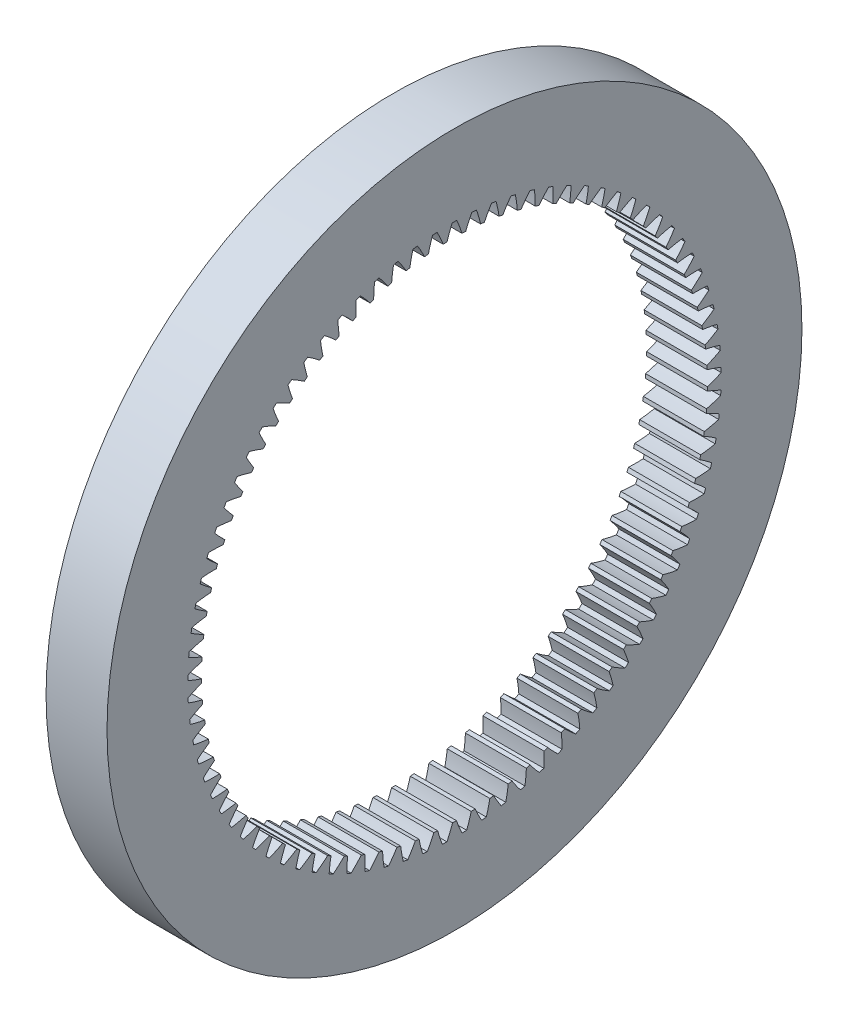
SolidWorks part; units mm, degrees
ref_plane "Plane1" through (0, 0, 0) normal (0, 0, 1) x (1, 0, 0)
ref_plane "Plane2" through (0, 0, 0) normal (0, 1, 0) x (1, 0, 0)
ref_plane "Plane3" through (0, 0, 0) normal (1, 0, 0) x (0, 0, -1)
sketch "HoldingSke" plane through (0, 0, 0) normal (0, 1, 0) x (1, 0, 0)
  line L0 (0, 0) -> (0.1743, -1.9924)
  line L1 (-15, 0) -> (100, 0) construction
  line L2 (0, 0) -> (-2.1039, 2.3779)
  line L3 (0, 0) -> (-11.863, 4.5341)
  line L4 (0, 0) -> (0.7527, 8.6031)
  line L5 (0, 0) -> (-23.7986, -8.8762)
  line L6 (0, 0) -> (-10.5278, -7.1032)
  line L7 (-2.1039, 2.3779) -> (3.3635, 27.1825)
  line L8 (-76.2, 2.8779) -> (-54.61, 2.8779)
  line L9 (-71.009, 38.7566) -> (-53.1078, 45.2721)
  line L10 (-76.2, 71.12) -> (104.1128, 71.12)
  line L11 (0, 0) -> (-5, 0)
  line L12 (-76.2, 101.6) -> (-76.181, 101.6)
  line L13 (24.9733, 27.94) -> (52.9518, 28.4284)
  line L14 (24.9733, 27.94) -> (24.9743, 27.94)
  line L15 (24.9733, 27.94) -> (100.4006, 29.5858)
  circle A0 centre (0, 0) radius 28.5
  circle A1 centre (0, 0) radius 12.7
  circle A2 centre (0, 0) radius 12.7
  dimension "Num_teeth" = 85
  dimension "Pitch_radius" = 180.3128
  dimension "Width" = 5
  dimension "Diameter" = 57
sketch "BasProSke" plane through (0, 0, 0) normal (0, 1, 0) x (1, 0, 0)
  line L0 (-10, 0) -> (60, 0) construction
  line L1 (0, 20.75) -> (0, 28.5)
  line L2 (0, 20.75) -> (5, 20.75)
  line L3 (5, 20.75) -> (5, 28.5)
  line L4 (5, 28.5) -> (0, 28.5)
  dimension "Thickness" = 5
  dimension "Diameter" = 57
revolve "Base-Revolve" add sketch "BasProSke" angle 360 about L0
sketch "TooCutSke" plane through (0, 0, 0) normal (1, 0, 0) x (0, 0, -1)
  line L3 (0.4402, 21.2454) -> (0.4402, 53.6633) construction
  line L4 (0, 0) -> (0, 59.563) construction
  line L5 (0, 0) -> (-2.5248, 68.2808) construction
  line L6 (-9.551, 17.6307) -> (37.1529, 19.3577) construction
  circle A0 centre (0, 0) radius 21.25 construction
  circle A1 centre (0, 0) radius 21.876 construction
  circle A2 centre (0, 0) radius 17.9716 construction
  circle A3 centre (0, 0) radius 20.7246 construction
  arc A4 (0.6163, 20.7154) -> (0.1893, 21.8752) centre (-9.551, 17.6307) ccw
  arc A5 (0.6163, 20.7154) -> (-0.6163, 20.7154) centre (0, 0) ccw
  arc A6 (0.1893, 21.8752) -> (-0.1893, 21.8752) centre (0, 0) ccw
  arc A7 (-0.1893, 21.8752) -> (-0.6163, 20.7154) centre (9.551, 17.6307) ccw
extrude "ToothCut" cut sketch "TooCutSke" along normal through all
fillet "Breaks" [suppressed] radius 0.05
fillet "RootFillets" [suppressed] radius 0.126
pattern_circular "TeethCuts" count 85 every 4.235 about axis through (-10, 0, 0) along (1, 0, 0) of "RootFillets", "Breaks", "ToothCut"
equation "' \"Module@HoldingSke\" = 6.35"
equation "' \"Num_teeth@HoldingSke\" = 24"
equation "' \"Ap@HoldingSke\" =  14.5"
equation "' \"Ap@HoldingSke\" = 14.5"
equation "' \"Width@HoldingSke\" = 12"
equation "' \"Diameter@HoldingSke\" = 8 * 25.4"
equation "' \"Show_teeth@HoldingSke\" = 100"
equation "' \"Backlash@HoldingSke\" = 0.009 * 25.4"
equation "' \"Addendum_fac@HoldingSke\" = 1.0"
equation "' \"Dedendum_fac@HoldingSke\" = 1.25"
equation "' \"Dedendum_add@HoldingSke\" = 0.00005 * 25.4"
equation "' \"Clearance_fac@HoldingSke\" = 0.25"
equation "\"Pitch@HoldingSke\" = 1 / \"Module@HoldingSke\" "
equation "\"Overcut_dia@TooCutSke\" = (\"Num_teeth@HoldingSke\" - 2 * \"Addendum_fac@HoldingSke\") / \"Pitch@HoldingSke\" - 0.002 * 25.4"
equation "\"Pitch_dia@TooCutSke\" = \"Num_teeth@HoldingSke\" / \"Pitch@HoldingSke\""
equation "\"Base_dia@TooCutSke\" = \"Num_teeth@HoldingSke\" / \"Pitch@HoldingSke\" * cos((\"Ap@HoldingSke\"  * 3.14159265 / 180)) * 0.90"
equation "\"Root_dia@TooCutSke\" = \"Num_teeth@HoldingSke\"  / \"Pitch@HoldingSke\" + 2 *  \"Dedendum_fac@HoldingSke\"/ \"Pitch@HoldingSke\" + \"Dedendum_add@HoldingSke\" * 2"
equation "\"Half_ang@TooCutSke\" = 180 / \"Num_teeth@HoldingSke\""
equation "\"Half_CT@TooCutSke\" = \"Num_teeth@HoldingSke\" / \"Pitch@HoldingSke\" * sin((3.14159265 / 2 / \"Num_teeth@HoldingSke\")) / 2 + 10 * \"Backlash@HoldingSke\" / 4"
equation "\"Flank_rad@TooCutSke\" = \"Num_teeth@HoldingSke\" / \"Pitch@HoldingSke\" / 4"
equation "\"Radius@RootFillets\"= \"Clearance_fac@HoldingSke\" / \"Pitch@HoldingSke\" + \"Dedendum_add@HoldingSke\""
equation "\"Break_rad@Breaks\" = 0.02 / \"Pitch@HoldingSke\" * 5"
equation "\"Num_teeth@TeethCuts\" = int( \"Show_teeth@HoldingSke\" ) + 1"
equation "\"Num_teeth@TeethCuts\" = ((sgn( \"Num_teeth@TeethCuts\" - \"Num_teeth@HoldingSke\" )-1)*( \"Num_teeth@TeethCuts\" - \"Num_teeth@HoldingSke\" ))/-2+ \"Num_teeth@HoldingSke\""
equation "\"Num_teeth@TeethCuts\" = ((sgn( \"Num_teeth@TeethCuts\" - 2.0)+1)*( \"Num_teeth@TeethCuts\" - 2.0))/2 +2.0"
equation "\"Angle@TeethCuts\" = 360.0 / \"Num_teeth@HoldingSke\""
equation "\"Diameter@BasProSke\" = \"Num_teeth@HoldingSke\"  / \"Pitch@HoldingSke\" + 2 *  \"Dedendum_fac@HoldingSke\"/ \"Pitch@HoldingSke\" + \"Dedendum_add@HoldingSke\" * 2 + 0.002 * 25.4"
equation "\"Diameter@BasProSke\" = ((sgn( \"Diameter@BasProSke\"  - \"Diameter@HoldingSke\" )+1)*( \"Diameter@BasProSke\"  - \"Diameter@HoldingSke\" ))/2 + \"Diameter@HoldingSke\""
equation "\"Inside_diameter@BasProSke\" =  (\"Num_teeth@HoldingSke\" - 2 * \"Addendum_fac@HoldingSke\") / \"Pitch@HoldingSke\" "
equation "\"Thickness@BasProSke\"  = \"Width@HoldingSke\""
